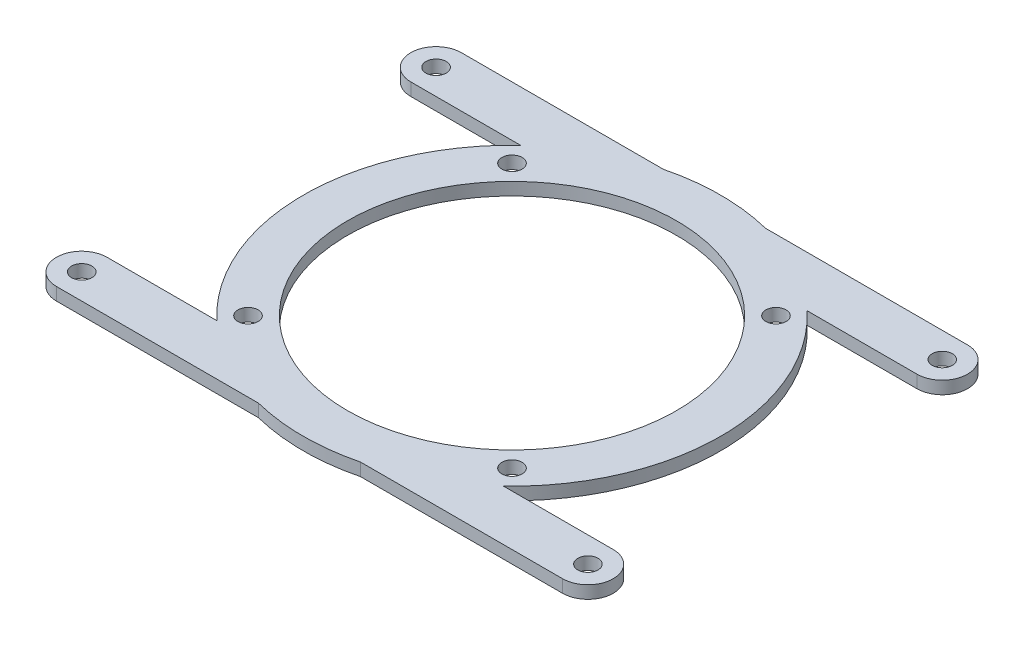
SolidWorks part; units mm, degrees
ref_plane "Front Plane" through (0, 0, 0) normal (0, 0, 1) x (1, 0, 0)
ref_plane "Top Plane" through (0, 0, 0) normal (0, 1, 0) x (1, 0, 0)
ref_plane "Right Plane" through (0, 0, 0) normal (1, 0, 0) x (0, 0, -1)
sketch "Sketch1" plane through (0, 0, 0) normal (0, 1, 0) x (1, 0, 0)
  line L1 (0, 4.2426) -> (-16.1407, 20.3833)
  line L3 (-51.9438, 37.8284) -> (-29.2993, 15.1839)
  line L4 (57.6006, 32.1716) -> (32.2808, 6.8518)
  line L5 (-57.6006, 32.1716) -> (-32.2808, 6.8518)
  line L6 (51.9438, 37.8284) -> (29.2993, 15.1839)
  line L7 (51.9438, -37.8284) -> (29.2993, -15.1839)
  line L8 (57.6006, -32.1716) -> (32.2808, -6.8518)
  line L9 (-57.6006, -32.1716) -> (-32.2808, -6.8518)
  line L10 (-51.9438, -37.8284) -> (-29.2993, -15.1839)
  line L11 (0, 4.2426) -> (16.1407, 20.3833)
  line L13 (0, -4.2426) -> (-16.1407, -20.3833)
  line L15 (0, -4.2426) -> (16.1407, -20.3833)
  line L16 (4.2426, 0) -> (20.3833, -16.1407)
  line L17 (-4.2426, 0) -> (-20.3833, -16.1407)
  line L18 (-4.2426, 0) -> (-20.3833, 16.1407)
  line L19 (4.2426, 0) -> (20.3833, 16.1407)
  circle A0 centre (54.7722, 35) radius 1.6
  arc A1 (57.6006, 32.1716) -> (51.9438, 37.8284) centre (54.7722, 35) ccw
  circle A2 centre (-54.7722, 35) radius 1.6
  arc A3 (-57.6006, 32.1716) -> (-51.9438, 37.8284) centre (-54.7722, 35) cw
  arc A4 (57.6006, -32.1716) -> (51.9438, -37.8284) centre (54.7722, -35) cw
  circle A5 centre (54.7722, -35) radius 1.6
  arc A6 (-57.6006, -32.1716) -> (-51.9438, -37.8284) centre (-54.7722, -35) ccw
  circle A7 centre (-54.7722, -35) radius 1.6
  arc A8 (-29.2993, -15.1839) -> (29.2993, -15.1839) centre (0, 0) ccw
  arc A9 (-20.3833, 16.1407) -> (-20.3833, -16.1407) centre (0, 0) ccw
  arc A11 (-32.2808, 6.8518) -> (-32.2808, -6.8518) centre (0, 0) ccw
  arc A12 (29.2993, 15.1839) -> (-29.2993, 15.1839) centre (0, 0) ccw
  arc A13 (32.2808, -6.8518) -> (32.2808, 6.8518) centre (0, 0) ccw
  circle A14 centre (20.8597, 20.8597) radius 1.6
  circle A15 centre (-20.8597, 20.8597) radius 1.6
  circle A16 centre (20.8597, -20.8597) radius 1.6
  circle A17 centre (-20.8597, -20.8597) radius 1.6
  arc A18 (16.1407, 20.3833) -> (-16.1407, 20.3833) centre (0, 0) ccw
  arc A19 (20.3833, -16.1407) -> (20.3833, 16.1407) centre (0, 0) ccw
  arc A20 (-16.1407, -20.3833) -> (16.1407, -20.3833) centre (0, 0) ccw
extrude "Boss-Extrude1" add sketch "Sketch1" along normal blind 2
sketch "Sketch2" plane through (0, 2, 0) normal (0, 1, 0) x (1, 0, 0)
  circle A0 centre (0, 0) radius 42
  circle A1 centre (0, 0) radius 48
  circle A3 centre (31.8198, 31.8198) radius 1.6
  circle A4 centre (-31.8198, 31.8198) radius 1.6
  circle A5 centre (31.8198, -31.8198) radius 1.6
  circle A6 centre (-31.8198, -31.8198) radius 1.6
extrude "Boss-Extrude2" add sketch "Sketch2" against normal up to surface (2 mm away) up to face at (-20.8597, 0, 22.4597)
sketch "Sketch3" plane through (0, 2, 0) normal (0, 1, 0) x (1, 0, 0)
  line L1 (34.8198, 31.8198) -> (34.8198, -31.8198)
  line L2 (-28.8198, -31.8198) -> (-28.8198, 31.8198)
  line L4 (-34.8198, 31.8198) -> (-34.8198, -31.8198)
  line L5 (28.8198, -31.8198) -> (28.8198, 31.8198)
  arc A0 (-34.8198, -31.8198) -> (-28.8198, -31.8198) centre (-31.8198, -31.8198) ccw
  arc A1 (-28.8198, 31.8198) -> (-34.8198, 31.8198) centre (-31.8198, 31.8198) ccw
  circle A2 centre (-31.8198, 31.8198) radius 1.6
  circle A3 centre (-31.8198, -31.8198) radius 1.6
  circle A4 centre (31.8198, -31.8198) radius 1.6
  circle A5 centre (31.8198, 31.8198) radius 1.6
  arc A6 (28.8198, 31.8198) -> (34.8198, 31.8198) centre (31.8198, 31.8198) cw
  arc A7 (34.8198, -31.8198) -> (28.8198, -31.8198) centre (31.8198, -31.8198) cw
extrude "Boss-Extrude3" add sketch "Sketch3" against normal up to surface (2 mm away) up to face at (-54.7722, 0, 36.6)
sketch "Sketch4" plane through (0, 2, 0) normal (0, 1, 0) x (1, 0, 0)
  line L0 (-28.8198, 31.8198) -> (-28.8198, 24.7402)
  line L1 (28.8198, -31.8198) -> (28.8198, -27.4437)
  line L2 (28.8198, 31.8198) -> (28.8198, 53.4887)
  line L3 (28.8198, 53.4887) -> (-28.8198, 53.4887)
  line L4 (-28.8198, 53.4887) -> (-28.8198, 31.8198)
  line L5 (-28.8198, -31.8198) -> (-28.8198, -57.6782)
  line L6 (-28.8198, -57.6782) -> (28.8198, -57.6782)
  line L7 (28.8198, -57.6782) -> (28.8198, -31.8198)
  line L8 (-28.8198, 24.7402) -> (0, 38.8462)
  line L9 (0, 38.8462) -> (28.8198, 24.7402)
  line L10 (-28.8198, -27.4437) -> (0, -37.5923)
  line L11 (0, -37.5923) -> (28.8198, -27.4437)
  line L12 (-28.8198, -27.4437) -> (-28.8198, -31.8198)
  line L13 (28.8198, 24.7402) -> (28.8198, 31.8198)
extrude "Cut-Extrude1" cut sketch "Sketch4" against normal blind 10
fillet "Fillet1" radius 3 4 edges at (-28.8198, 1, -38.3851) (28.8198, 1, -38.3851) (28.8198, 1, 38.3851) (-28.8198, 1, 38.3851)
sketch "Sketch5" plane through (0, 2, 0) normal (0, 1, 0) x (1, 0, 0)
  line L0 (-31.8198, 34.8198) -> (31.8198, 34.8198)
  line L2 (0, 28.8198) -> (28.8198, 28.8198)
  line L3 (28.8198, 31.8198) -> (28.8198, 16.0754) construction
  line L4 (28.8198, 28.8198) -> (28.8198, 31.8198)
  line L5 (28.8198, 31.8198) -> (29.7534, 32.7534)
  line L6 (29.7534, 32.7534) -> (31.8198, 34.8198)
  line L7 (0, 28.8198) -> (-28.8198, 28.8198)
  line L8 (-28.8198, 16.0754) -> (-28.8198, 31.8198) construction
  line L9 (-28.8198, 28.8198) -> (-28.8198, 31.8198)
  line L10 (-28.8198, 31.8198) -> (-31.8198, 34.8198)
  line L12 (-28.8198, -31.8198) -> (-31.8198, -34.8198)
  line L13 (-28.8198, -28.8198) -> (-28.8198, -31.8198)
  line L14 (0, -28.8198) -> (-28.8198, -28.8198)
  line L15 (29.7534, -32.7534) -> (31.8198, -34.8198)
  line L16 (28.8198, -31.8198) -> (29.7534, -32.7534)
  line L17 (28.8198, -28.8198) -> (28.8198, -31.8198)
  line L18 (0, -28.8198) -> (28.8198, -28.8198)
  line L20 (-31.8198, -34.8198) -> (31.8198, -34.8198)
  arc A0 (-28.8198, 31.8198) -> (-33.9411, 33.9411) centre (-31.8198, 31.8198) ccw construction
  arc A1 (33.9411, 33.9411) -> (28.8198, 31.8198) centre (31.8198, 31.8198) ccw construction
extrude "Boss-Extrude4" add sketch "Sketch5" against normal up to surface (2 mm away) up to face at (0, 0, 0)
sketch "Sketch6" plane through (0, 2, 0) normal (0, 1, 0) x (1, 0, 0)
  circle A0 centre (0, 0) radius 26
extrude "Cut-Extrude2" cut sketch "Sketch6" against normal blind 10
sketch "Sketch7" plane through (0, 2, 0) normal (0, 1, 0) x (1, 0, 0)
  circle A0 centre (0, 0) radius 26
  circle A1 centre (0, 0) radius 33
  circle A2 centre (0, 0) radius 112.7408
extrude "Cut-Extrude3" cut sketch "Sketch7" against normal blind 10 contours A2 A1 region at (-109.552, 2, 0)
sketch "Sketch8" plane through (0, 2, 0) normal (0, 1, 0) x (1, 0, 0)
  line L2 (60, 32) -> (-60, 32)
  line L3 (60, 24) -> (22.6495, 24)
  line L4 (22.6495, 24) -> (0, 32)
  line L5 (-60, 24) -> (-22.6495, 24)
  line L6 (-22.6495, 24) -> (0, 32)
  line L8 (-22.6495, -24) -> (0, -32)
  line L9 (-60, -24) -> (-22.6495, -24)
  line L10 (22.6495, -24) -> (0, -32)
  line L11 (60, -24) -> (22.6495, -24)
  line L12 (60, -32) -> (-60, -32)
  circle A0 centre (60, 28) radius 1.6
  arc A1 (60, 24) -> (60, 32) centre (60, 28) ccw
  circle A2 centre (0, 0) radius 33 construction
  arc A3 (-60, 24) -> (-60, 32) centre (-60, 28) cw
  circle A4 centre (-60, 28) radius 1.6
  circle A5 centre (-60, -28) radius 1.6
  arc A6 (-60, -24) -> (-60, -32) centre (-60, -28) ccw
  arc A7 (60, -24) -> (60, -32) centre (60, -28) cw
  circle A8 centre (60, -28) radius 1.6
  circle M2 centre (-20.8597, -20.8597) radius 1.6
  circle M3 centre (-20.8597, 20.8597) radius 1.6
  circle M4 centre (20.8597, 20.8597) radius 1.6
  circle M5 centre (20.8597, -20.8597) radius 1.6
  circle M6 centre (0, 0) radius 26
  circle M7 centre (0, 0) radius 33
extrude "Boss-Extrude5" add sketch "Sketch8" against normal up to surface (2 mm away) contours L3 A1 L2 A0 M7 | A3 L5 L2 A4 M7 | L9 A6 L12 A5 M7 | A7 L11 L12 A8 M7 | L10 L4 L6 L8 M7 M3 M5 M6 M4 M2 region at (39.3764, 2, -28.2024) region at (11.0186, 2, -27.1331) region at (-39.3764, 2, -28.2024) region at (-39.3764, 2, 28.2024) region at (39.3764, 2, 28.2024) up to face at (0, 0, 26)
sketch "Sketch9" plane through (0, 2, 0) normal (0, 1, 0) x (1, 0, 0)
  line L0 (-40, 32) -> (-88.8012, 51.8274)
  line L1 (-88.8012, 51.8274) -> (-77.9032, 7.2375)
  line L2 (-77.9032, 7.2375) -> (-40, 24)
  line L4 (-40, -24) -> (-110.0997, -14.9691)
  line L5 (-110.0997, -14.9691) -> (-87.8134, -65.3624)
  line L6 (-87.8134, -65.3624) -> (-40, -32)
  line L8 (40, -32) -> (82.7809, -58.2558)
  line L9 (82.7809, -58.2558) -> (126.8633, 11.4486)
  line L10 (126.8633, 11.4486) -> (40, -24)
  line L12 (40, 24) -> (64.9569, 7.2375)
  line L13 (64.9569, 7.2375) -> (132.4333, 44.8685)
  line L14 (132.4333, 44.8685) -> (31.2187, 101.8414)
  line L15 (31.2187, 101.8414) -> (40, 32)
  arc A0 (40, 24) -> (40, 32) centre (40, 28) ccw
  circle A1 centre (40, 28) radius 1.6
  circle A2 centre (-40, 28) radius 1.6
  arc A3 (-40, 24) -> (-40, 32) centre (-40, 28) cw
  arc A4 (-40, -24) -> (-40, -32) centre (-40, -28) ccw
  circle A5 centre (-40, -28) radius 1.6
  circle A6 centre (40, -28) radius 1.6
  arc A7 (40, -24) -> (40, -32) centre (40, -28) cw
extrude "Cut-Extrude4" cut sketch "Sketch9" against normal blind 5
